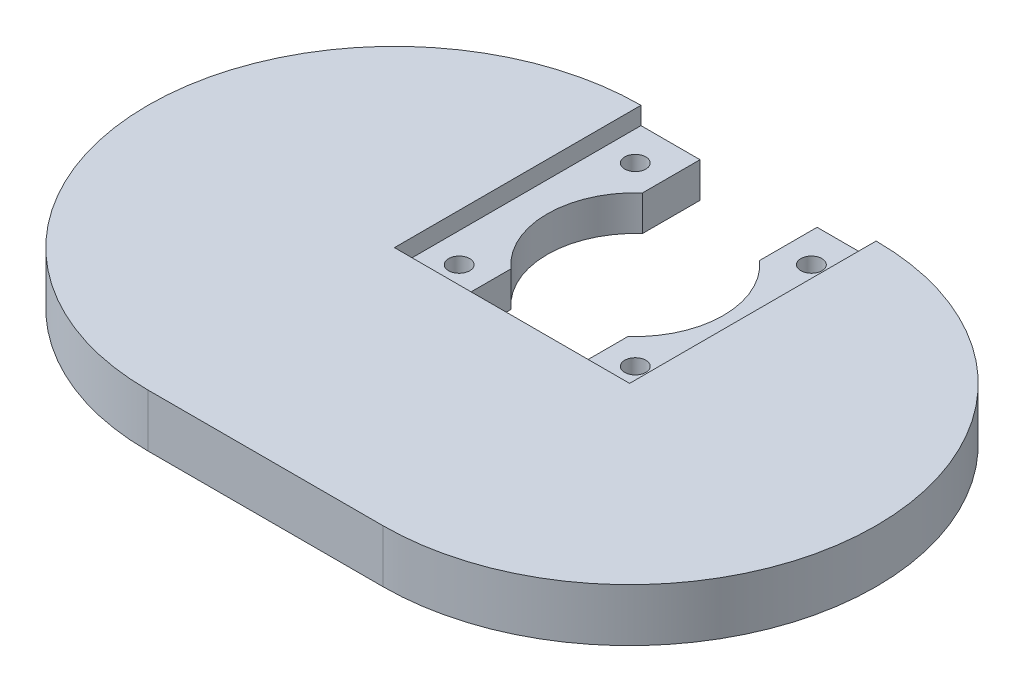
SolidWorks part; units mm, degrees
ref_plane "Front Plane" through (0, 0, 0) normal (0, 0, 1) x (1, 0, 0)
ref_plane "Top Plane" through (0, 0, 0) normal (0, 1, 0) x (1, 0, 0)
ref_plane "Right Plane" through (0, 0, 0) normal (1, 0, 0) x (0, 0, -1)
sketch "Sketch1" plane through (0, 0, 0) normal (0, 1, 0) x (1, 0, 0)
  line L0 (-61.1268, 24.4014) -> (-52.7465, 24.4014)
  line L1 (-69.507, 59.4014) -> (-52.7465, 59.4014)
  line L2 (-69.507, 59.4014) -> (-69.507, -10.5986)
  line L3 (-69.507, -10.5986) -> (-52.7465, -10.5986)
  line L4 (-52.7465, 59.4014) -> (-52.7465, -10.5986)
  line L5 (-69.507, 59.4014) -> (-52.7465, -10.5986) construction
  line L6 (-69.507, -10.5986) -> (-52.7465, 59.4014) construction
  line L7 (-69.507, 24.4014) -> (-52.7465, 24.4014)
  line L8 (-61.1268, 59.4014) -> (-61.1268, -10.5986)
  circle A0 centre (-61.1268, 49.4014) radius 3
  circle A1 centre (-61.1268, -0.5986) radius 3
  point P0 (-61.1268, 24.4014)
  dimension "D2" = 8.3803
  dimension "D1" = 70
  dimension "D3" = 16.7606
  dimension "D6" = 50
extrude "Boss-Extrude1" add sketch "Sketch1" against normal blind 10 contours L1 L4 L3 L2
extrude "Cut-Extrude1" cut sketch "Sketch1<3>" against normal blind 20 contours A0 | A1
sketch "Sketch1<3>" plane through (0, 0, 0) normal (0, 1, 0) x (1, 0, 0) same geometry as "Sketch1"
sketch "Sketch3" plane through (-10.4418, 0, 0) normal (0, 1, 0) x (1, 0, 0)
  line L0 (-0.6859, 24.4014) -> (7.6944, 24.4014)
  line L1 (-9.0662, 59.4014) -> (7.6944, 59.4014)
  line L2 (-9.0662, 59.4014) -> (-9.0662, -10.5986)
  line L3 (-9.0662, -10.5986) -> (7.6944, -10.5986)
  line L4 (7.6944, 59.4014) -> (7.6944, -10.5986)
  line L5 (-9.0662, 59.4014) -> (7.6944, -10.5986) construction
  line L6 (-9.0662, -10.5986) -> (7.6944, 59.4014) construction
  line L7 (-9.0662, 24.4014) -> (7.6944, 24.4014)
  line L8 (-0.6859, 59.4014) -> (-0.6859, -10.5986)
  circle A0 centre (-0.6859, 49.4014) radius 3
  circle A1 centre (-0.6859, -0.5986) radius 3
  point P0 (-0.6859, 24.4014)
  dimension "D2" = 8.3803
  dimension "D1" = 70
  dimension "D3" = 16.7606
  dimension "D6" = 50
extrude "Boss-Extrude2" add sketch "Sketch3" against normal blind 10 separate body contours A0 L8 L0 L4 L1 | A0 L8 L1 L2 L7 | L8 A1 L7 L2 L3 | L8 A1 L3 L4 L0 region at (-6.7899, 0, -41.5216) region at (-15.4656, 0, -7.2812) region at (-15.4656, 0, -41.5216) region at (-6.7899, 0, -7.2812)
sketch "Sketch8" plane through (0, 0, 0) normal (0, 1, 0) x (1, 0, 0)
  line L0 (-2.7475, 59.4014) -> (-2.7475, -10.5986)
  line L1 (-2.7475, -10.5986) -> (-19.508, -10.5986)
  line L2 (-19.508, -10.5986) -> (-52.7465, -10.5986)
  line L3 (-52.7465, -10.5986) -> (-69.507, -10.5986)
  line L4 (-69.507, -10.5986) -> (-69.507, 59.4014)
  line L5 (-69.507, 59.4014) -> (-52.7465, 59.4014)
  line L6 (-69.507, -80.5986) -> (-2.7475, -80.5986)
  line L7 (-19.508, 59.4014) -> (-19.508, -10.5986) construction
  arc A0 (-69.507, 59.4014) -> (-69.507, -80.5986) centre (-69.507, -10.5986) ccw
  arc A1 (-2.7475, 59.4014) -> (-2.7475, -80.5986) centre (-2.7475, -10.5986) cw
  point P18 (-36.1272, -10.5986)
  point P19 (-19.508, 24.4014)
  point P20 (-36.1272, 24.4014)
  dimension "D1" = 70
sketch "Sketch9" plane through (0, 0, 0) normal (0, 1, 0) x (1, 0, 0)
  line L0 (-19.508, 59.4014) -> (-19.508, -10.5986) construction
  circle A0 centre (-36.1272, 24.4014) radius 24.9995
  point P0 (-11.1277, -0.5986)
  point P1 (-19.508, 24.4014)
  point P3 (-11.1277, 24.4014)
extrude "Cut-Extrude4" cut sketch "Sketch9" against normal blind 11 contours A0
extrude "Boss-Extrude4" add sketch "Sketch8" against normal blind 10 and the other way blind 5 contours L4 L3 L2 L1 L0 A1 L6 A0
